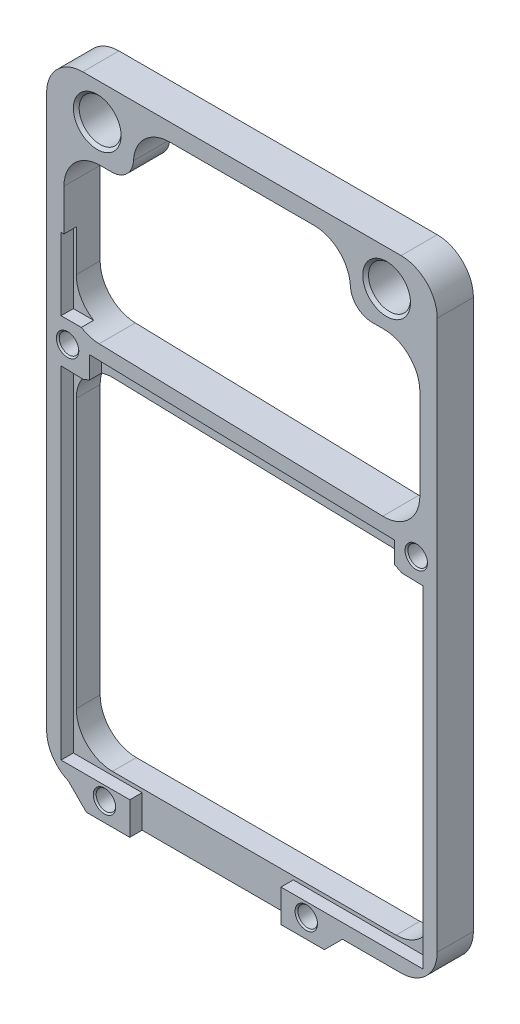
SolidWorks part; units mm, degrees
ref_plane "Front" through (0, 0, 0) normal (0, 0, 1) x (1, 0, 0)
ref_plane "Top" through (0, 0, 0) normal (0, 1, 0) x (1, 0, 0)
ref_plane "Right" through (0, 0, 0) normal (1, 0, 0) x (0, 0, -1)
sketch "Sketch1" plane through (0, 0, 0) normal (0, 0, 1) x (1, 0, 0)
  line L0 (0, 78.4) -> (54, 78.4) construction
  line L1 (0, 0) -> (54, 0)
  line L2 (0, 0) -> (0, 83.4)
  line L3 (5, 88.4) -> (49, 88.4)
  line L4 (54, 0) -> (54, 83.4)
  line L5 (27, 8.5492) -> (27, -24.6289) construction
  circle A0 centre (7, 83.4) radius 2.9
  circle A1 centre (47, 83.4) radius 2.9
  arc A2 (49, 88.4) -> (54, 83.4) centre (49, 83.4) cw
  arc A3 (5, 88.4) -> (0, 83.4) centre (5, 83.4) ccw
  circle A4 centre (2.9, 54.7) radius 1.35
  circle A5 centre (51.1, 53.4) radius 1.35
  circle A6 centre (8, 2.6) radius 1.35
  circle A7 centre (35.9, 2.6) radius 1.35
  dimension "D1" = 5.8
  dimension "D6" = 5
  dimension "D8" = 2.7
  dimension "D10" = 5.1
  dimension "D12" = 50.8
  dimension "D13" = 15.2
  dimension "D14" = 24.1
  dimension "D16" = 25
  dimension "D17" = 2.6
  dimension "D2" = 40
  dimension "D3" = 7
  dimension "D4" = 5
  dimension "D5" = 7
  dimension "D7" = 10
  dimension "D9" = 27.9
  dimension "D11" = 1.3
  dimension "D15" = 27
extrude "Boss-Extrude1" add sketch "Sketch1" along normal blind 5
sketch "Sketch2" plane through (0, 0, 5) normal (0, 0, 1) x (1, 0, 0)
  line L0 (5.5, 0) -> (3, 2.5)
  line L1 (0, 0) -> (54, 0) construction
  line L2 (3, 2.5) -> (0, 2.5)
  line L3 (0, 83.4) -> (0, 0) construction
  line L4 (0, 2.5) -> (0, 0)
  line L5 (0, 0) -> (5.5, 0)
  line L6 (38.4, 0) -> (40.9, 2.5)
  line L7 (40.9, 2.5) -> (54, 2.5)
  line L8 (54, 0) -> (54, 83.4) construction
  line L9 (54, 2.5) -> (54, 0)
  line L10 (54, 0) -> (38.4, 0)
  circle A0 centre (8, 2.6) radius 1.35 construction
  circle A1 centre (35.9, 2.6) radius 1.35 construction
  dimension "D3" = 5
  dimension "D1" = 2.5
  dimension "D2" = 45
  dimension "D4" = 5
extrude "Cut-Extrude1" cut sketch "Sketch2" against normal blind 5
sketch "Sketch3" plane through (0, 0, 5) normal (0, 0, 1) x (1, 0, 0)
  line L0 (12, 81) -> (12, 78.4)
  line L1 (12, 78.4) -> (7.4, 78.4)
  line L2 (2.4, 73.4) -> (2.4, 61.9696)
  line L3 (7.2679, 56.9714) -> (46.4679, 55.9356)
  line L4 (51.6, 60.9339) -> (51.6, 73.4)
  line L5 (46.6, 78.4) -> (42, 78.4)
  line L6 (42, 78.4) -> (42, 81)
  line L7 (37, 86) -> (17, 86)
  line L8 (49, 88.4) -> (5, 88.4) construction
  line L9 (54, 2.5) -> (54, 83.4) construction
  line L10 (0, 83.4) -> (0, 2.5) construction
  line L11 (7.5321, 52.1644) -> (46.7321, 51.1286)
  line L12 (51.6, 46.1304) -> (51.6, 10)
  line L13 (46.6, 5) -> (7.4, 5)
  line L14 (2.4, 10) -> (2.4, 47.1661)
  circle A0 centre (7, 83.4) radius 2.9 construction
  circle A1 centre (47, 83.4) radius 2.9 construction
  circle A3 centre (2.9, 54.7) radius 1.35 construction
  circle A4 centre (51.1, 53.4) radius 1.35 construction
  circle A5 centre (8, 2.6) radius 1.35 construction
  arc A6 (51.6, 10) -> (46.6, 5) centre (46.6, 10) cw
  arc A7 (7.4, 5) -> (2.4, 10) centre (7.4, 10) cw
  arc A8 (2.4, 47.1661) -> (7.5321, 52.1644) centre (7.4, 47.1661) cw
  arc A9 (51.6, 46.1304) -> (46.7321, 51.1286) centre (46.6, 46.1304) ccw
  arc A10 (51.6, 60.9339) -> (46.4679, 55.9356) centre (46.6, 60.9339) cw
  arc A11 (2.4, 61.9696) -> (7.2679, 56.9714) centre (7.4, 61.9696) ccw
  arc A12 (2.4, 73.4) -> (7.4, 78.4) centre (7.4, 73.4) cw
  arc A13 (51.6, 73.4) -> (46.6, 78.4) centre (46.6, 73.4) ccw
  arc A14 (42, 81) -> (37, 86) centre (37, 81) ccw
  arc A15 (12, 81) -> (17, 86) centre (17, 81) cw
  point P34 (2.4, 52.3)
  point P37 (51.6, 51)
  point P40 (51.6, 55.8)
  point P43 (2.4, 57.1)
  dimension "D3" = 5
  dimension "D7" = 2.4
  dimension "D13" = 2.4
  dimension "D14" = 5
  dimension "D1" = 5
  dimension "D2" = 5
  dimension "D4" = 2.4
  dimension "D5" = 2.4
  dimension "D6" = 2.4
  dimension "D8" = 2.4
  dimension "D9" = 2.4
  dimension "D10" = 2.4
  dimension "D11" = 2.4
  dimension "D12" = 2.4
extrude "Cut-Extrude2" cut sketch "Sketch3" against normal blind 5
chamfer "Chamfer1" distance 0.4 angle 45 4 edges at (49.9, 83.4, 0) (49.9, 83.4, 5) (9.9, 83.4, 0) (9.9, 83.4, 5)
chamfer "Chamfer2" distance 0.2 angle 45 8 edges at (37.25, 2.6, 0) (37.25, 2.6, 5) (9.35, 2.6, 0) (9.35, 2.6, 5) (52.45, 53.4, 0) (52.45, 53.4, 5) (4.25, 54.7, 0) (4.25, 54.7, 5)
fillet "Fillet1" radius 3 2 edges at (42, 78.4, 2.5) (12, 78.4, 2.5)
fillet "Fillet2" radius 5 2 edges at (54, 2.5, 2.5) (0, 2.5, 2.5)
sketch "Sketch4" plane through (0, 0, 5) normal (0, 0, 1) x (1, 0, 0)
  line L5 (7.4, 5) -> (46.6, 5) construction
  line L6 (11.5, 5) -> (32.4, 5)
  line L7 (11.5, 5) -> (11.5, 0)
  line L8 (11.5, 0) -> (32.4, 0)
  line L9 (32.4, 5) -> (32.4, 0)
  line L10 (5.5, 0) -> (38.4, 0) construction
  circle A0 centre (8, 2.6) radius 1.35 construction
  circle A1 centre (35.9, 2.6) radius 1.35 construction
  dimension "D1" = 3.5
  dimension "D2" = 3.5
extrude "Cut-Extrude3" cut sketch "Sketch4" against normal blind 1.7
sketch "Sketch5" plane through (0, 0, 5) normal (0, 0, 1) x (1, 0, 0)
  line L0 (0, 83.4) -> (0, 7.0826) construction
  line L1 (2, 51.6963) -> (52, 50.3752)
  line L2 (2, 51.6963) -> (2, 4.5)
  line L3 (2, 4.5) -> (52, 4.5)
  line L4 (52, 50.3752) -> (52, 4.5)
  line L5 (54, 7.5) -> (54, 83.4) construction
  line L8 (2.4, 73.4) -> (2.4, 61.9696) construction
  line L9 (2, 57.7) -> (10, 57.7)
  line L10 (2, 57.7) -> (2, 67.6848)
  line L11 (2, 67.6848) -> (10, 67.6848)
  line L12 (10, 57.7) -> (10, 67.6848)
  line L13 (46.7321, 51.1286) -> (7.5321, 52.1644) construction
  line L14 (49, 2.5) -> (40.9, 2.5) construction
  circle A0 centre (2.9, 54.7) radius 1.35 construction
  circle A4 centre (51.1, 53.4) radius 1.35 construction
  point P20 (2.4, 67.6848)
  dimension "D6" = 3
  dimension "D1" = 2
  dimension "D2" = 2
  dimension "D3" = 2
  dimension "D4" = 2
  dimension "D5" = 8
  dimension "D7" = 3
extrude "Cut-Extrude5" cut sketch "Sketch5" against normal blind 1.7
sketch "Sketch6" plane through (0, 0, 5) normal (0, 0, 1) x (1, 0, 0)
  line L0 (48.1, 53.8918) -> (5.9, 55.0068)
  line L1 (5.9, 55.0068) -> (5.9, 50.5538)
  line L2 (5.9, 50.5538) -> (48.1, 49.4388)
  line L3 (48.1, 49.4388) -> (48.1, 53.8918)
  line L4 (46.7321, 51.1286) -> (7.5321, 52.1644) construction
  line L5 (7.2679, 56.9714) -> (46.4679, 55.9356) construction
  circle A0 centre (51.1, 53.4) radius 1.35 construction
  circle A1 centre (2.9, 54.7) radius 1.35 construction
  dimension "D1" = 3
  dimension "D2" = 3
  dimension "D3" = 2
extrude "Cut-Extrude6" cut sketch "Sketch6" against normal up to surface (1.7 mm away) up to face at (25.7489, 21.5047, 3.3)
